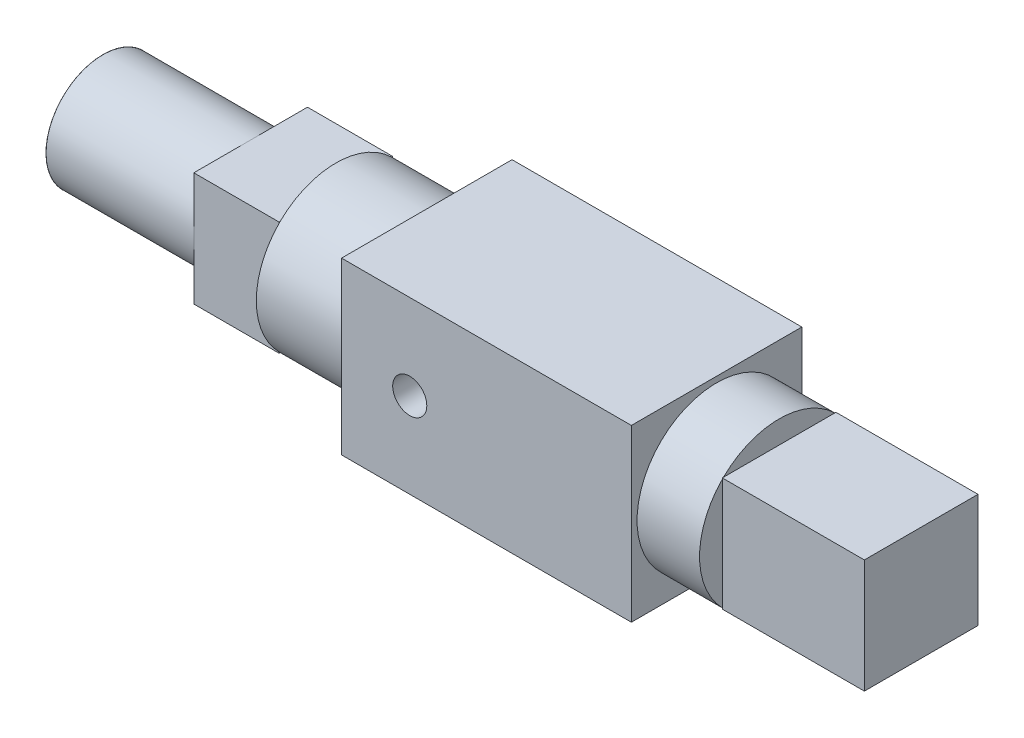
SolidWorks part; units mm, degrees
ref_plane "Piano frontale" through (0, 0, 0) normal (0, 0, 1) x (1, 0, 0)
ref_plane "Piano superiore" through (0, 0, 0) normal (0, 1, 0) x (1, 0, 0)
ref_plane "Piano destro" through (0, 0, 0) normal (1, 0, 0) x (0, 0, -1)
sketch "Schizzo1" plane through (0, 0, 0) normal (1, 0, 0) x (0, 0, -1)
  line L1 (-7.5, -7.5) -> (7.5, -7.5)
  line L2 (-7.5, -7.5) -> (-7.5, 7.5)
  line L3 (-7.5, 7.5) -> (7.5, 7.5)
  line L4 (7.5, -7.5) -> (7.5, 7.5)
  line L5 (-7.5, -7.5) -> (7.5, 7.5) construction
  line L6 (-7.5, 7.5) -> (7.5, -7.5) construction
  point P0 (0, 0)
  dimension "D1" = 15
extrude "Estrusione-Estrusione1" add sketch "Schizzo1" along normal blind 72
sketch "Schizzo2" plane through (0, 0, 0) normal (-1, 0, 0) x (0, 0, 1)
  line L4 (-7.5, 7.5) -> (-7.5, -7.5)
  line L5 (-7.5, -7.5) -> (7.5, -7.5)
  line L6 (7.5, -7.5) -> (7.5, 7.5)
  line L7 (7.5, 7.5) -> (-7.5, 7.5)
  line L8 (-7.5, 7.5) -> (-7.5, -7.5)
  line L9 (-7.5, -7.5) -> (7.5, -7.5)
  line L10 (7.5, -7.5) -> (7.5, 7.5)
  line L11 (7.5, 7.5) -> (-7.5, 7.5)
  circle A0 centre (0, 0) radius 5
  dimension "D2" = 10
  dimension "D1" = 0
extrude "Taglio-Estrusione1" cut sketch "Schizzo2" against normal blind 13
sketch "Schizzo3" plane through (13, 0, 0) normal (-1, 0, 0) x (0, 0, 1)
  line L1 (-5, -5) -> (5, -5)
  line L2 (-5, -5) -> (-5, 5)
  line L3 (-5, 5) -> (5, 5)
  line L4 (5, -5) -> (5, 5)
  line L5 (-5, -5) -> (5, 5) construction
  line L6 (-5, 5) -> (5, -5) construction
  line L10 (7.5, 7.5) -> (-7.5, 7.5)
  line L11 (-7.5, 7.5) -> (-7.5, -7.5)
  line L12 (-7.5, -7.5) -> (7.5, -7.5)
  line L13 (7.5, -7.5) -> (7.5, 7.5)
  line L14 (7.5, 7.5) -> (-7.5, 7.5)
  line L15 (-7.5, 7.5) -> (-7.5, -7.5)
  line L16 (-7.5, -7.5) -> (7.5, -7.5)
  line L17 (7.5, -7.5) -> (7.5, 7.5)
  point P0 (0, 0)
  dimension "D1" = 10
  dimension "D2" = 0
extrude "Taglio-Estrusione2" cut sketch "Schizzo3" against normal blind 7.5
sketch "Schizzo4" plane through (20.5, 0, 0) normal (-1, 0, 0) x (0, 0, 1)
  line L4 (7.5, -7.5) -> (7.5, 7.5)
  line L5 (7.5, 7.5) -> (-7.5, 7.5)
  line L6 (-7.5, 7.5) -> (-7.5, -7.5)
  line L7 (-7.5, -7.5) -> (7.5, -7.5)
  line L8 (7.5, -7.5) -> (7.5, 7.5)
  line L9 (7.5, 7.5) -> (-7.5, 7.5)
  line L10 (-7.5, 7.5) -> (-7.5, -7.5)
  line L11 (-7.5, -7.5) -> (7.5, -7.5)
  circle A0 centre (0, 0) radius 7
  dimension "D2" = 14
  dimension "D1" = 0
extrude "Taglio-Estrusione3" cut sketch "Schizzo4" against normal blind 8
sketch "Schizzo5" plane through (0, 0, 0) normal (0, 0, 1) x (1, 0, 0)
  line L0 (0, 5.009) -> (0, -5.009)
  line L1 (0, 0) -> (-1.3, 0) construction
  arc A0 (0, 5.009) -> (0, -5.009) centre (9, 0) ccw
  dimension "D2" = 20.6
  dimension "D1" = 9
revolve "Rivoluzione1" add sketch "Schizzo5" angle 360 about L1 region at (-0.5229, 1.8953, 0)
sketch "Schizzo6" plane through (72, 0, 0) normal (1, 0, 0) x (0, 0, -1)
  line L1 (-5, -5) -> (5, -5)
  line L2 (-5, -5) -> (-5, 5)
  line L3 (-5, 5) -> (5, 5)
  line L4 (7.5, -7.5) -> (7.5, 7.5)
  line L5 (7.5, 7.5) -> (-7.5, 7.5)
  line L6 (-7.5, 7.5) -> (-7.5, -7.5)
  line L7 (-7.5, -7.5) -> (7.5, -7.5)
  line L8 (7.5, -7.5) -> (7.5, 7.5)
  line L9 (7.5, 7.5) -> (-7.5, 7.5)
  line L10 (-7.5, 7.5) -> (-7.5, -7.5)
  line L11 (-7.5, -7.5) -> (7.5, -7.5)
  line L12 (5, -5) -> (5, 5)
  line L13 (-5, -5) -> (5, 5) construction
  line L14 (-5, 5) -> (5, -5) construction
  point P0 (0, 0)
  point P10 (0, 0)
  dimension "D1" = 10
  dimension "D2" = 0
extrude "Taglio-Estrusione4" cut sketch "Schizzo6" against normal blind 12.5
sketch "Schizzo8" plane through (59.5, 0, 0) normal (1, 0, 0) x (0, 0, -1)
  line L4 (-7.5, -7.5) -> (7.5, -7.5)
  line L5 (7.5, -7.5) -> (7.5, 7.5)
  line L6 (7.5, 7.5) -> (-7.5, 7.5)
  line L7 (-7.5, 7.5) -> (-7.5, -7.5)
  line L8 (-7.5, -7.5) -> (7.5, -7.5)
  line L9 (7.5, -7.5) -> (7.5, 7.5)
  line L10 (7.5, 7.5) -> (-7.5, 7.5)
  line L11 (-7.5, 7.5) -> (-7.5, -7.5)
  circle A0 centre (0, 0) radius 7
  dimension "D1" = 14
  dimension "D2" = 0
extrude "Taglio-Estrusione5" cut sketch "Schizzo8" against normal blind 5.5
sketch "Schizzo9" plane through (0, 0, 0) normal (0, 0, 1) x (1, 0, 0)
  line L0 (28.5, -7.5) -> (28.5, 7.5) construction
  circle A0 centre (34.5, 0) radius 1.5
  point P4 (0, 0)
  dimension "D2" = 3
  dimension "D1" = 6
extrude "Taglio-Estrusione6" cut sketch "Schizzo9" against normal through all both and the other way through all
